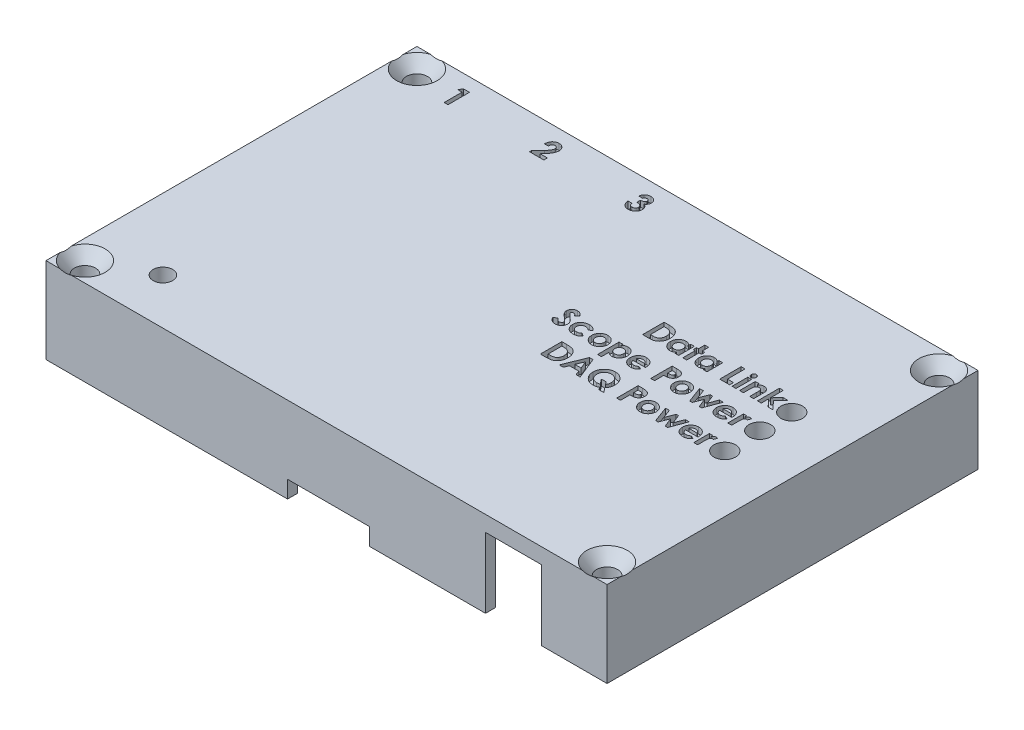
SolidWorks part; units mm, degrees
ref_plane "Front Plane" through (0, 0, 0) normal (0, 0, 1) x (1, 0, 0)
ref_plane "Top Plane" through (0, 0, 0) normal (0, 1, 0) x (1, 0, 0)
ref_plane "Right Plane" through (0, 0, 0) normal (1, 0, 0) x (0, 0, -1)
sketch "Sketch1" plane through (0, 0, 0) normal (0, 1, 0) x (1, 0, 0)
  line L1 (45.72, 30.226) -> (-45.72, 30.226)
  line L2 (45.72, 30.226) -> (45.72, -30.226)
  line L3 (45.72, -30.226) -> (-45.72, -30.226)
  line L4 (-45.72, 30.226) -> (-45.72, -30.226)
  line L5 (45.72, 30.226) -> (-45.72, -30.226) construction
  line L6 (45.72, -30.226) -> (-45.72, 30.226) construction
  point P0 (0, 0)
  dimension "D1" = 60.452
  dimension "D2" = 91.44
extrude "Boss-Extrude1" add sketch "Sketch1" along normal blind 13.97
sketch "Sketch2" plane through (0, 0, 0) normal (0, -1, 0) x (1, 0, 0)
  line L0 (45.72, -30.226) -> (-45.72, -30.226) construction
  line L1 (39.37, 28.575) -> (-39.37, 28.575)
  line L2 (39.37, 28.575) -> (39.37, -28.575)
  line L3 (39.37, -28.575) -> (-39.37, -28.575)
  line L4 (-39.37, 28.575) -> (-39.37, -28.575)
  line L5 (39.37, 28.575) -> (-39.37, -28.575) construction
  line L6 (39.37, -28.575) -> (-39.37, 28.575) construction
  line L7 (-45.72, -30.226) -> (-45.72, 30.226) construction
  point P0 (0, 0)
  dimension "D1" = 1.651
  dimension "D2" = 57.15
  dimension "D3" = 78.74
  dimension "D4" = 6.35
extrude "Cut-Extrude1" cut sketch "Sketch2" against normal offset from surface (11.43 mm away) 2.54 up to face at (0, 13.97, 0)
sketch "Sketch3" plane through (0, 0, 0) normal (0, -1, 0) x (1, 0, 0)
  line L0 (42.545, 27.051) -> (-42.545, 27.051) construction
  line L1 (42.545, 27.051) -> (42.545, -27.051) construction
  line L2 (42.545, -27.051) -> (-42.545, -27.051) construction
  line L3 (-42.545, 27.051) -> (-42.545, -27.051) construction
  line L4 (42.545, 27.051) -> (-42.545, -27.051) construction
  line L5 (42.545, -27.051) -> (-42.545, 27.051) construction
  line L6 (-45.72, 30.226) -> (45.72, 30.226) construction
  line L7 (-45.72, -30.226) -> (-45.72, 30.226) construction
  line L9 (-45.72, -30.226) -> (-45.72, 30.226) construction
  line L10 (39.37, 28.575) -> (-39.37, 28.575) construction
  circle A0 centre (-42.545, 27.051) radius 1.7145
  circle A1 centre (-42.545, -27.051) radius 1.7145
  circle A2 centre (42.545, -27.051) radius 1.7145
  circle A3 centre (42.545, 27.051) radius 1.7145
  circle A4 centre (-34.163, 22.733) radius 1.5875
  point P0 (0, 0)
  dimension "D1" = 3.429
  dimension "D5" = 11.557
  dimension "D6" = 3.175
  dimension "D2" = 3.175
  dimension "D3" = 3.175
  dimension "D4" = 5.842
extrude "Cut-Extrude2" cut sketch "Sketch3" against normal through all
chamfer "Chamfer1" distance 1.905 distance2 1.5875 4 edges at (42.545, 13.97, -28.7655) (42.545, 13.97, 25.3365) (-42.545, 13.97, 25.3365) (-42.545, 13.97, -28.7655) first distance on face at (42.545, 13.97, -28.7655) first distance on face at (42.545, 13.97, 25.3365) first distance on face at (-42.545, 13.97, 25.3365) first distance on face at (-42.545, 13.97, -28.7655)
sketch "Sketch4" plane through (0, 0, 30.226) normal (0, 0, 1) x (1, 0, 0)
  line L0 (-45.72, 0) -> (45.72, 0) construction
  line L1 (-6.35, 0) -> (6.985, 0)
  line L2 (-6.35, 0) -> (-6.35, 2.794)
  line L3 (-6.35, 2.794) -> (6.985, 2.794)
  line L4 (6.985, 0) -> (6.985, 2.794)
  line L5 (45.72, 13.97) -> (45.72, 0) construction
  line L6 (-45.72, 13.97) -> (-45.72, 0) construction
  line L7 (35.052, 11.43) -> (25.908, 11.43)
  line L8 (35.052, 11.43) -> (35.052, 0)
  line L9 (35.052, 0) -> (25.908, 0)
  line L10 (25.908, 11.43) -> (25.908, 0)
  line L11 (35.052, 11.43) -> (25.908, 0) construction
  line L12 (35.052, 0) -> (25.908, 11.43) construction
  point P8 (30.48, 5.715)
  dimension "D1" = 13.335
  dimension "D2" = 2.794
  dimension "D3" = 52.07
  dimension "D4" = 76.2
  dimension "D5" = 11.43
  dimension "D6" = 9.144
extrude "Cut-Extrude3" cut sketch "Sketch4" against normal up to next
sketch "Sketch5" plane through (0, 0, -30.226) normal (0, 0, -1) x (-1, 0, 0)
  line L0 (-45.72, 0) -> (45.72, 0) construction
  line L1 (-6.6548, 0) -> (-2.7432, 0)
  line L2 (-6.6548, 0) -> (-6.6548, 1.4478)
  line L3 (-6.6548, 1.4478) -> (-2.7432, 1.4478)
  line L4 (-2.7432, 0) -> (-2.7432, 1.4478)
  line L5 (5.461, 6.604) -> (20.32, 6.604) construction
  line L6 (20.32, 6.604) -> (35.179, 6.604) construction
  line L7 (45.72, 13.97) -> (45.72, 0) construction
  line L8 (-4.699, 1.4478) -> (-4.699, 0) construction
  line L9 (2.286, 6.604) -> (2.286, 0)
  line L10 (2.286, 0) -> (8.636, 0)
  line L11 (8.636, 6.604) -> (8.636, 0)
  line L12 (-27.0547, 10.0965) -> (-31.3653, 10.0965)
  line L13 (17.145, 6.604) -> (17.145, 0)
  line L14 (17.145, 0) -> (23.495, 0)
  line L15 (23.495, 6.604) -> (23.495, 0)
  line L16 (-45.72, 13.97) -> (-45.72, 0) construction
  line L17 (32.004, 6.604) -> (32.004, 0)
  line L18 (32.004, 0) -> (38.354, 0)
  line L19 (38.354, 6.604) -> (38.354, 0)
  line L20 (-41.638, 13.97) -> (41.638, 13.97) construction
  arc A0 (8.636, 6.604) -> (2.286, 6.604) centre (5.461, 6.604) ccw
  arc A1 (23.495, 6.604) -> (17.145, 6.604) centre (20.32, 6.604) ccw
  arc A2 (38.354, 6.604) -> (32.004, 6.604) centre (35.179, 6.604) ccw
  arc A3 (-31.3653, 10.0965) -> (-27.0547, 10.0965) centre (-29.21, 7.4295) ccw
  dimension "D1" = 6.35
  dimension "D9" = 6.858
  dimension "D2" = 1.4478
  dimension "D3" = 3.9116
  dimension "D4" = 6.604
  dimension "D5" = 10.541
  dimension "D6" = 25.4
  dimension "D7" = 50.419
  dimension "D8" = 40.259
  dimension "D10" = 2.667
  dimension "D11" = 16.51
  dimension "D12" = 6.5405
extrude "Cut-Extrude4" cut sketch "Sketch5" against normal up to next
fillet "Fillet1" radius 1.5875 4 edges at (-39.37, 5.715, -28.575) (-39.37, 5.715, 28.575) (39.37, 5.715, 28.575) (39.37, 5.715, -28.575)
sketch "Sketch6" plane through (0, 11.43, 0) normal (0, -1, 0) x (1, 0, 0)
  line L1 (36.449, -9.144) -> (36.449, -3.937) construction
  line L2 (36.449, -3.937) -> (36.449, 1.778) construction
  line L3 (-45.72, -26.144) -> (-45.72, 26.144) construction
  line L4 (37.7825, 28.575) -> (35.052, 28.575) construction
  circle A0 centre (36.449, -9.144) radius 1.75
  circle A1 centre (36.449, -3.937) radius 1.75
  circle A2 centre (36.449, 1.778) radius 1.75
  dimension "D1" = 3.5
  dimension "D2" = 82.169
  dimension "D3" = 26.797
  dimension "D4" = 5.715
  dimension "D5" = 5.207
extrude "Cut-Extrude5" cut sketch "Sketch6" against normal up to next
sketch "Sketch7" plane through (0, 13.97, 0) normal (0, 1, 0) x (1, 0, 0)
  line L0 (-36.7154, 24.5407) -> (-21.7777, 24.5407) construction
  line L1 (-21.7777, 24.5407) -> (-6.8399, 24.5407) construction
  line L2 (12.9339, 7.9504) -> (3.4502, 7.9504) construction
  line L3 (3.4502, 7.9504) -> (3.4502, 2.4137) construction
  line L4 (3.4502, 2.4137) -> (3.4502, -3.123) construction
  line L5 (3.4502, -3.123) -> (7.3459, -3.123) construction
  text T0 "<b>Data Link</b>"
  text T1 "<b>Scope Power</b>"
  text T2 "<b>DAQ Power</b>"
  text T3 "<b>1</b>"
  text T4 "<b>2</b>"
  text T5 "<b>3</b>"
extrude "Cut-Extrude6" cut sketch "Sketch7" against normal blind 1
